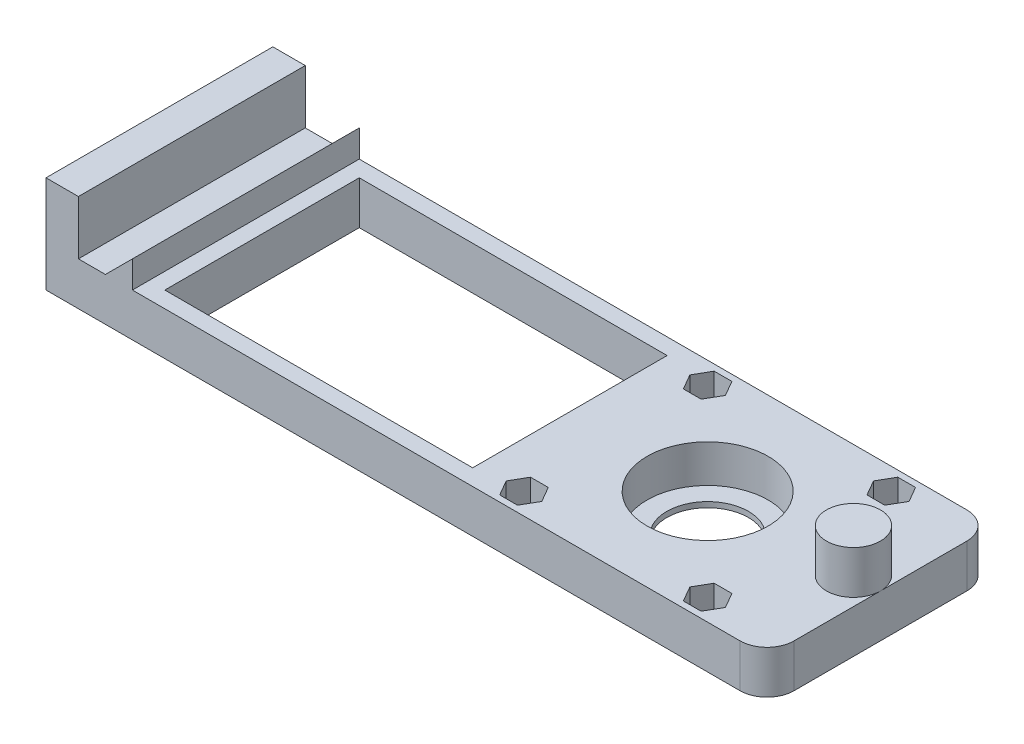
SolidWorks part; units mm, degrees
ref_plane "Front Plane" through (0, 0, 0) normal (0, 0, 1) x (1, 0, 0)
ref_plane "Top Plane" through (0, 0, 0) normal (0, 1, 0) x (1, 0, 0)
ref_plane "Right Plane" through (0, 0, 0) normal (1, 0, 0) x (0, 0, -1)
sketch "Sketch1" plane through (0, 0, 0) normal (0, 1, 0) x (1, 0, 0)
  line L1 (-61.75, -21) -> (61.75, -21)
  line L2 (-61.75, -21) -> (-61.75, 21)
  line L3 (-61.75, 21) -> (61.75, 21)
  line L4 (61.75, -21) -> (61.75, 21)
  line L5 (-61.75, -21) -> (61.75, 21) construction
  line L6 (-61.75, 21) -> (61.75, -21) construction
  point P0 (0, 0)
  dimension "D1" = 123.5
  dimension "D2" = 42
extrude "Boss-Extrude1" add sketch "Sketch1" along normal blind 8
sketch "Sketch2" plane through (0, 8, 0) normal (0, 1, 0) x (1, 0, 0)
  line L0 (61.75, 0) -> (39.75, 0) construction
  line L1 (61.75, -21) -> (61.75, 21) construction
  circle A0 centre (39.75, 0) radius 11.2
  dimension "D2" = 22.4
  dimension "D1" = 22
extrude "Cut-Extrude1" cut sketch "Sketch2" against normal blind 7
sketch "Sketch3" plane through (0, 0, 0) normal (0, -1, 0) x (1, 0, 0)
  line L0 (61.75, 0) -> (39.75, 0) construction
  line L1 (61.75, 21) -> (61.75, -21) construction
  circle A0 centre (39.75, 0) radius 7.55
  dimension "D2" = 15.1
  dimension "D1" = 22
extrude "Cut-Extrude2" cut sketch "Sketch3" against normal up to next
sketch "Sketch9" plane through (0, 8, 0) normal (0, 1, 0) x (1, 0, 0)
  line L0 (56.75, 21) -> (56.75, 17) construction
  line L1 (61.75, 21) -> (-61.75, 21) construction
  line L2 (56.75, 17) -> (61.75, 17) construction
  line L3 (61.75, -21) -> (61.75, 21) construction
  line L4 (61.75, 0) -> (39.75, 0) construction
  line L5 (39.75, 0) -> (39.75, 21) construction
  line L6 (61.75, 21) -> (-61.75, 21) construction
  line L7 (58.3954, 19.85) -> (55.1046, 19.85)
  line L8 (55.1046, 19.85) -> (53.4591, 17)
  line L9 (53.4591, 17) -> (55.1046, 14.15)
  line L10 (55.1046, 14.15) -> (58.3954, 14.15)
  line L11 (58.3954, 14.15) -> (60.0409, 17)
  line L12 (60.0409, 17) -> (58.3954, 19.85)
  line L13 (60.0409, -17) -> (58.3954, -19.85)
  line L14 (58.3954, -19.85) -> (55.1046, -19.85)
  line L15 (55.1046, -19.85) -> (53.4591, -17)
  line L16 (53.4591, -17) -> (55.1046, -14.15)
  line L17 (55.1046, -14.15) -> (58.3954, -14.15)
  line L18 (58.3954, -14.15) -> (60.0409, -17)
  line L19 (19.4591, 17) -> (21.1046, 19.85)
  line L20 (21.1046, 19.85) -> (24.3954, 19.85)
  line L21 (24.3954, 19.85) -> (26.0409, 17)
  line L22 (26.0409, 17) -> (24.3954, 14.15)
  line L23 (24.3954, 14.15) -> (21.1046, 14.15)
  line L24 (21.1046, 14.15) -> (19.4591, 17)
  line L25 (21.1046, -14.15) -> (19.4591, -17)
  line L26 (24.3954, -14.15) -> (21.1046, -14.15)
  line L27 (26.0409, -17) -> (24.3954, -14.15)
  line L28 (24.3954, -19.85) -> (26.0409, -17)
  line L29 (21.1046, -19.85) -> (24.3954, -19.85)
  line L30 (19.4591, -17) -> (21.1046, -19.85)
  circle A7 centre (56.75, 17) radius 2.85 construction
  point P4 (59.2182, 15.575)
  dimension "D3" = 5.7
  dimension "D1" = 4
  dimension "D2" = 5
  dimension "D4" = 0
extrude "Cut-Extrude4" cut sketch "Sketch9" against normal blind 6
sketch "Sketch10" plane through (0, 0, 0) normal (0, -1, 0) x (1, 0, 0)
  line L0 (56.75, 21) -> (56.75, 17) construction
  line L1 (-61.75, 21) -> (61.75, 21) construction
  line L2 (56.75, 17) -> (61.75, 17) construction
  line L3 (61.75, 21) -> (61.75, -21) construction
  line L4 (39.75, 0) -> (39.75, 21) construction
  line L23 (39.75, 0) -> (61.75, 0) construction
  circle A1 centre (56.75, 17) radius 1.75
  circle A3 centre (22.75, 17) radius 1.75
  circle A4 centre (56.75, -17) radius 1.75
  circle A5 centre (22.75, -17) radius 1.75
  dimension "D3" = 3.5
  dimension "D1" = 4
  dimension "D2" = 5
extrude "Cut-Extrude5" cut sketch "Sketch10" against normal blind 2
sketch "Sketch12" plane through (0, 0, -21) normal (0, 0, -1) x (-1, 0, 0)
  line L0 (55.75, 8) -> (50.75, 8) construction
  line L1 (61.75, 8) -> (55.75, 8)
  line L2 (61.75, 8) -> (61.75, 18)
  line L3 (61.75, 18) -> (55.75, 18)
  line L4 (55.75, 8) -> (55.75, 18)
  line L5 (-61.75, 8) -> (61.75, 8) construction
  line L6 (50.75, 8) -> (45.75, 8)
  line L7 (45.75, 8) -> (45.75, 13)
  line L8 (45.75, 13) -> (50.75, 8)
  dimension "D1" = 10
  dimension "D2" = 6
  dimension "D3" = 5
  dimension "D4" = 5
  dimension "D5" = 5
extrude "Boss-Extrude2" add sketch "Sketch12" against normal up to surface (42 mm away) up to face at (0, 4, 21)
sketch "Sketch13" plane through (0, 8, 0) normal (0, 1, 0) x (1, 0, 0)
  line L0 (-42.75, 21) -> (-42.75, 18) construction
  line L1 (61.75, 21) -> (-45.75, 21) construction
  line L2 (-42.75, 18) -> (-45.75, 18) construction
  line L3 (-45.75, -21) -> (-45.75, 21) construction
  line L5 (-42.75, 18) -> (14.25, 18)
  line L6 (-42.75, 18) -> (-42.75, -18)
  line L7 (-42.75, -18) -> (14.25, -18)
  line L8 (14.25, 18) -> (14.25, -18)
  dimension "D1" = 3
  dimension "D2" = 3
  dimension "D3" = 36
  dimension "D4" = 57
extrude "Cut-Extrude6" cut sketch "Sketch13" against normal through all
sketch "Sketch23" plane through (0, 8, 0) normal (0, 1, 0) x (1, 0, 0)
  line L1 (61.75, 21) -> (71.75, 21)
  line L2 (61.75, 21) -> (61.75, -21)
  line L3 (61.75, -21) -> (71.75, -21)
  line L4 (71.75, 21) -> (71.75, -21)
  dimension "D1" = 42
  dimension "D2" = 10
extrude "Boss-Extrude3" add sketch "Sketch23" against normal blind 8
sketch "Sketch24" plane through (0, 8, 0) normal (0, 1, 0) x (1, 0, 0)
  line L0 (71.75, 0) -> (66.75, 0) construction
  line L1 (71.75, -21) -> (71.75, 21) construction
  circle A0 centre (66.75, 0) radius 5
  dimension "D1" = 5
extrude "Boss-Extrude4" add sketch "Sketch24" along normal blind 8
fillet "Fillet1" radius 5 2 edges at (71.75, 4, -21) (71.75, 4, 21)
